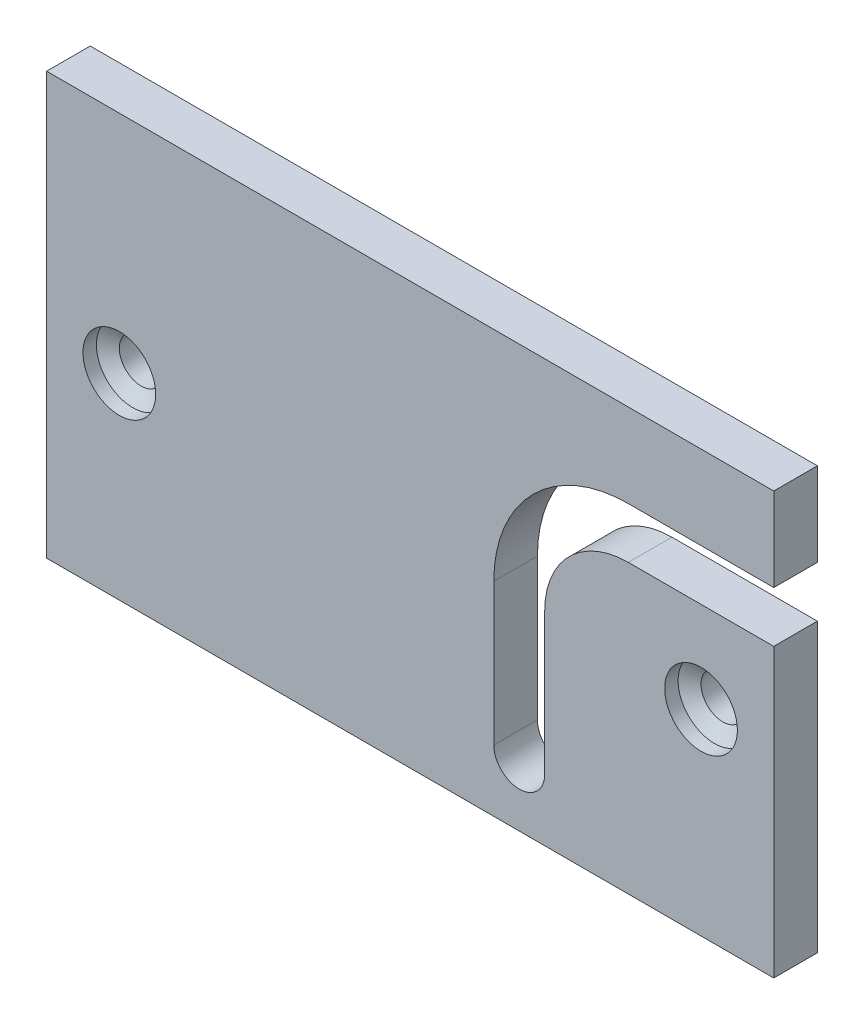
SolidWorks part; units mm, degrees
ref_plane "Спереди" through (0, 0, 0) normal (0, 0, 1) x (1, 0, 0)
ref_plane "Сверху" through (0, 0, 0) normal (0, 1, 0) x (1, 0, 0)
ref_plane "Справа" through (0, 0, 0) normal (1, 0, 0) x (0, 0, -1)
sketch "Эскиз1" plane through (0, 0, 0) normal (0, 0, 1) x (1, 0, 0)
  line L0 (0, 133.7222) -> (0, -128.0833) construction
  line L1 (-50, -29) -> (50, -29)
  line L2 (-50, -29) -> (-50, 29)
  line L3 (-50, 29) -> (50, 29)
  line L4 (50, -29) -> (50, 29)
  line L5 (-51.5556, 0) -> (155.4722, 0) construction
  dimension "D1" = 58
  dimension "D2" = 100
extrude "Бобышка-Вытянуть1" add sketch "Эскиз1" along normal mid plane 6
sketch "Эскиз2" plane through (0, 0, 3) normal (0, 0, 1) x (1, 0, 0)
  line L0 (-40, -2) -> (40, -2) construction
  line L1 (0, 0) -> (0, -2) construction
  circle A0 centre (-40, -2) radius 3
  circle A1 centre (40, -2) radius 3
  dimension "D2" = 6
  dimension "D1" = 80
  dimension "D3" = 2
extrude "Вырез-Вытянуть1" cut sketch "Эскиз2" against normal through all
sketch "Эскиз3" plane through (0, 0, 3) normal (0, 0, 1) x (1, 0, 0)
  circle A0 centre (-40, -2) radius 5
  circle A1 centre (40, -2) radius 5
  dimension "D1" = 10
extrude "Вырез-Вытянуть2" cut sketch "Эскиз3" against normal blind 1.5
chamfer "Фаска1" distance 1.5 angle 60 2 edges at (-37, -2, 1.5) (43, -2, 1.5) first distance on face at (-37, -2, -3) first distance on face at (43, -2, -3)
sketch "Эскиз4" plane through (0, 0, 3) normal (0, 0, 1) x (1, 0, 0)
  line L0 (15, -20.5) -> (15, -1) construction
  line L1 (30, 14) -> (54.8252, 14) construction
  line L2 (50, -29) -> (50, 29) construction
  line L3 (50, 29) -> (-50, 29) construction
  line L4 (18.5, -20.5) -> (18.5, -1)
  line L5 (30, 10.5) -> (54.8252, 10.5)
  line L6 (11.5, -20.5) -> (11.5, -1)
  line L7 (30, 17.5) -> (54.8252, 17.5)
  line L8 (0, 37.3071) -> (0, -38.4812) construction
  line L9 (-50, -29) -> (50, -29) construction
  line L10 (54.8252, 17.5) -> (54.8252, 10.5)
  arc A0 (15, -1) -> (30, 14) centre (30, -1) cw construction
  arc A1 (18.5, -1) -> (30, 10.5) centre (30, -1) cw
  arc A2 (11.5, -1) -> (30, 17.5) centre (30, -1) cw
  arc A4 (18.5, -20.5) -> (11.5, -20.5) centre (15, -20.5) cw
  line M8 (50, -29) -> (50, 29)
  dimension "D1" = 15
  dimension "D6" = 5
  dimension "D2" = 35
  dimension "D3" = 15
  dimension "D4" = 3.5
  dimension "D5" = 3.5
extrude "Вырез-Вытянуть4" cut sketch "Эскиз4" against normal through all contours A4 L4 A1 L5 L7 A2 L6 M8 region at (15, -23.4339, 3)
mirror "Зеркальное отражение2" [suppressed] of bodies 107
